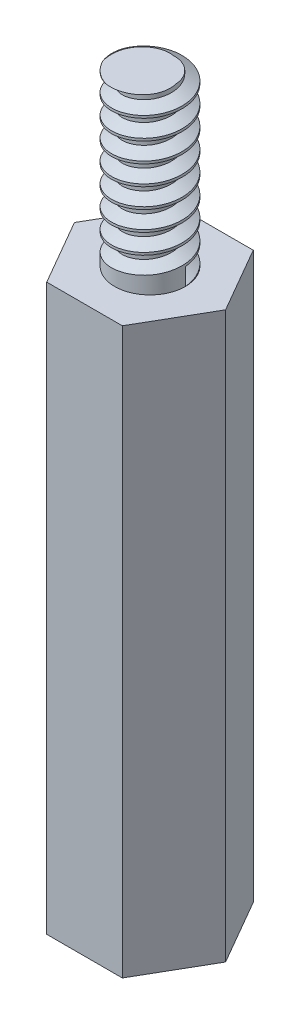
SolidWorks part; units mm, degrees
material "Brass"
ref_plane "Front Plane" through (0, 0, 0) normal (0, 0, 1) x (1, 0, 0)
ref_plane "Top Plane" through (0, 0, 0) normal (0, 1, 0) x (1, 0, 0)
ref_plane "Right Plane" through (0, 0, 0) normal (1, 0, 0) x (0, 0, -1)
sketch "Sketch1" plane through (0, 0, 0) normal (0, 1, 0) x (1, 0, 0)
  line L1 (1.3382, -2.3178) -> (2.6763, 0)
  line L2 (2.6763, 0) -> (1.3382, 2.3177)
  line L3 (1.3382, 2.3177) -> (-1.3382, 2.3178)
  line L4 (-1.3382, 2.3178) -> (-2.6763, 0)
  line L5 (-2.6763, 0) -> (-1.3382, -2.3177)
  line L6 (-1.3382, -2.3177) -> (1.3382, -2.3178)
  circle A0 centre (0, 0) radius 2.3178 construction
  dimension "D1" = 4.6355
extrude "Boss-Extrude1" add sketch "Sketch1" along normal blind 22.1
hole_wizard "CBORE for M2.5 Pan Head Machine Screw1" positions "Sketch2" profile "Sketch3" counterbore size "M2.5" standard "ANSI Metric"
sketch "Sketch2" plane through (0, 0, 0) normal (0, -1, 0) x (-1, 0, 0)
  point P0 (0, 0)
sketch "Sketch3" plane through (0, 0, 0) normal (1, 0, 0) x (0, 0, -1)
  line L0 (0, 0) -> (0, 12.8712)
  line L1 (0, 12.8712) -> (1.45, 12)
  line L2 (1.45, 12) -> (1.45, 2.1)
  line L3 (1.45, 2.1) -> (3, 2.1)
  line L4 (3, 2.1) -> (3, 0)
  line L5 (3, 0) -> (0, 0)
  line L10 (0, 12.8712) -> (-1.45, 12) construction
  line L11 (0, -6.35) -> (0, 107.95) construction
  dimension "Hole Dia." = 2.9
  dimension "Hole Depth" = 12
  dimension "C'Bore Dia." = 6
  dimension "C'Bore Depth" = 2.1
  dimension "Drill Angle" = 118
sketch "Sketch4" plane through (0, 22.1, 0) normal (0, 1, 0) x (1, 0, 0)
  circle A0 centre (0, 0) radius 1.25
  dimension "D1" = 2.5
extrude "Boss-Extrude2" add sketch "Sketch4" along normal blind 6
thread "Thread1" pitch 0.7 method cut profile "Thread Profile1" start angle 0, offset 0, length 10, pitch 0.7, diameter 2.5
ref_plane "Plane1" through (1.25, 22.1, 0) normal (0, 0, 1) x (1, 0, 0)
sketch "Thread Profile1" plane through (1.25, 22.1, 0) normal (0, 0, 1) x (1, 0, 0)
  line L0 (0, 0) -> (0, 0.7) construction
  line L11 (0, 0) -> (0, 0.6125)
  line L12 (0, 0.6125) -> (-0.3789, 0.3937)
  line L13 (-0.3789, 0.3937) -> (-0.3789, 0.2187)
  line L15 (-0.3789, 0.2187) -> (0, 0)
  line L17 (-0.3789, 0.3062) -> (0, 0.3062) construction
  point P2 (0, 0)
  dimension "Pitch" = 0.7
  dimension "Profile_Angle" = 60
  dimension "Profile_Land" = 0.175
  dimension "Profile_Height" = 0.3789
